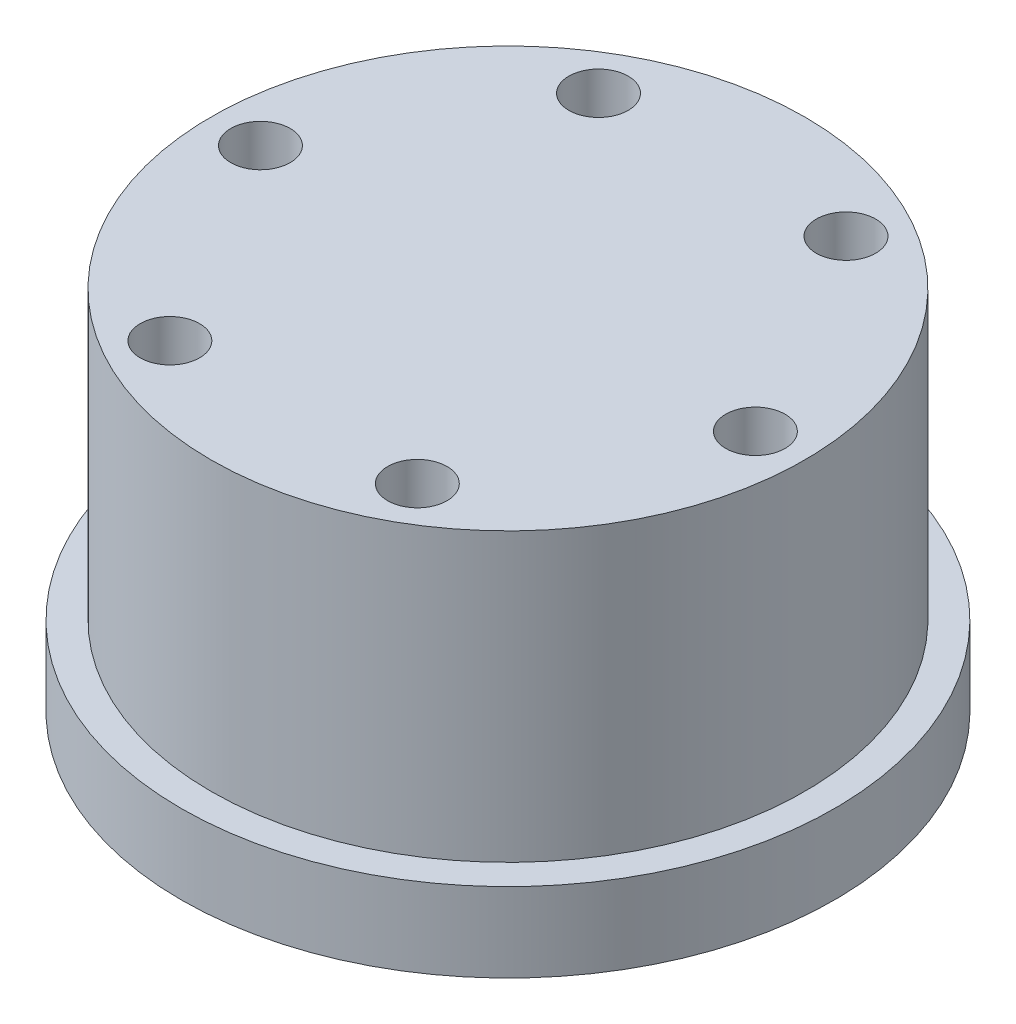
SolidWorks part; units mm, degrees
ref_plane "Front Plane" through (0, 0, 0) normal (0, 0, 1) x (1, 0, 0)
ref_plane "Top Plane" through (0, 0, 0) normal (0, 1, 0) x (1, 0, 0)
ref_plane "Right Plane" through (0, 0, 0) normal (1, 0, 0) x (0, 0, -1)
sketch "Sketch1" plane through (0, 0, 0) normal (0, 1, 0) x (1, 0, 0)
  circle A0 centre (0, 0) radius 16.5
  circle A1 centre (0, 0) radius 12.5 construction
  circle A2 centre (0, 12.5) radius 1.5
  circle A3 centre (10.8253, 6.25) radius 1.5
  circle A4 centre (10.8253, -6.25) radius 1.5
  circle A5 centre (0, -12.5) radius 1.5
  circle A6 centre (-10.8253, -6.25) radius 1.5
  circle A7 centre (-10.8253, 6.25) radius 1.5
  point P19 (0, 0)
  dimension "D1" = 33
  dimension "D2" = 25
  dimension "D3" = 3
  dimension "D4" = 6
extrude "Boss-Extrude1" add sketch "Sketch1" along normal blind 4
sketch "Sketch2" plane through (0, 4, 0) normal (0, 1, 0) x (1, 0, 0)
  circle A0 centre (0, 0) radius 15
  dimension "D1" = 30
extrude "Boss-Extrude2" add sketch "Sketch2" along normal blind 14.5
sketch "Sketch3" plane through (0, 0, 0) normal (0, -1, 0) x (1, 0, 0)
  circle A0 centre (0, 0) radius 9
  dimension "D1" = 18
extrude "Cut-Extrude1" cut sketch "Sketch3" against normal blind 2
sketch "Sketch4" plane through (0, 2, 0) normal (0, -1, 0) x (1, 0, 0)
  circle A0 centre (0, 0) radius 6.5
  dimension "D1" = 13
extrude "Cut-Extrude2" cut sketch "Sketch4" against normal blind 4
sketch "Sketch5" plane through (0, 18.5, 0) normal (0, 1, 0) x (1, 0, 0)
  circle A0 centre (0, 0) radius 12.5 construction
  circle A1 centre (-12.5, 0) radius 1.5
  circle A2 centre (-6.25, 10.8253) radius 1.5
  circle A3 centre (6.25, 10.8253) radius 1.5
  circle A4 centre (12.5, 0) radius 1.5
  circle A5 centre (6.25, -10.8253) radius 1.5
  circle A6 centre (-6.25, -10.8253) radius 1.5
  point P17 (0, 0)
  dimension "D1" = 25
  dimension "D2" = 3
  dimension "D3" = 6
extrude "Cut-Extrude3" cut sketch "Sketch5" against normal blind 5
